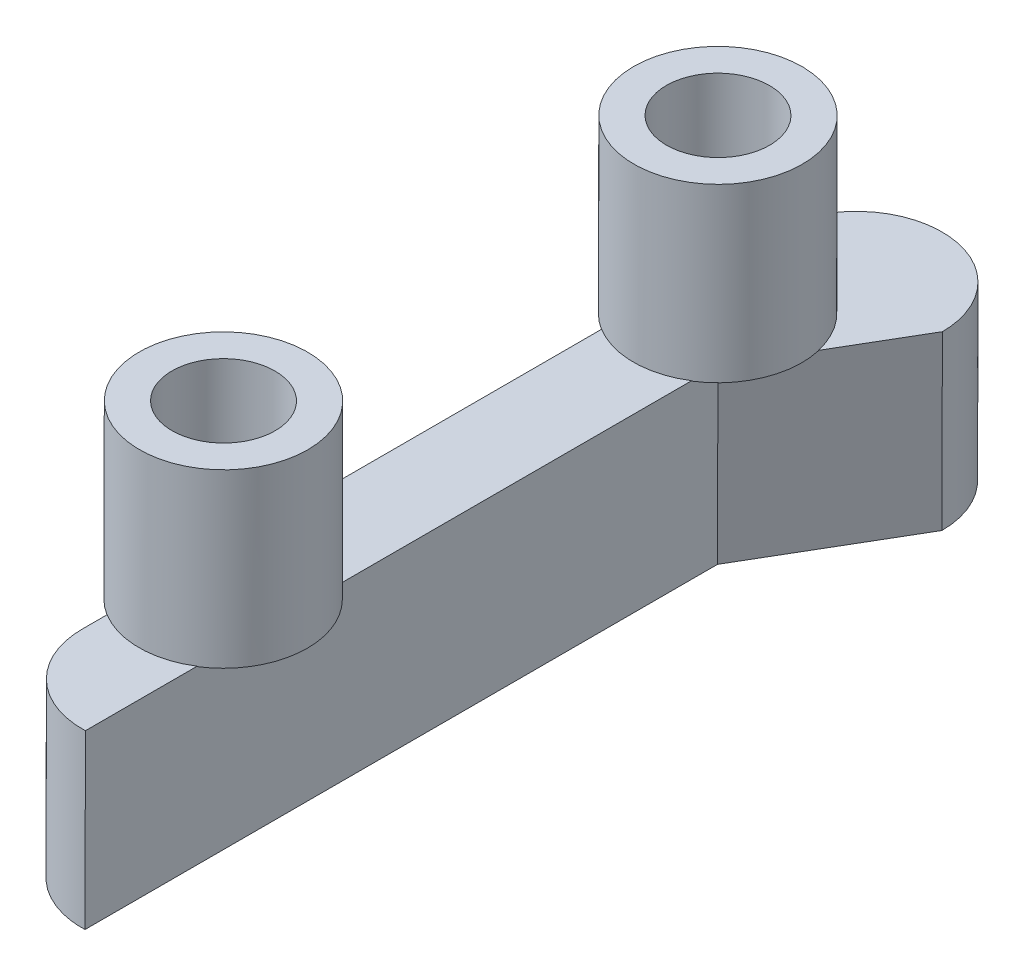
SolidWorks part; units mm, degrees
ref_plane "Front Plane" through (0, 0, 0) normal (0, 0, 1) x (1, 0, 0)
ref_plane "Top Plane" through (0, 0, 0) normal (0, 1, 0) x (1, 0, 0)
ref_plane "Right Plane" through (0, 0, 0) normal (1, 0, 0) x (0, 0, -1)
ref_plane "Plane1" through (0.2124, 88.2612, 0) normal (0.0024, 1, 0) x (1, -0.0024, 0)
sketch "Sketch1" plane through (0.2124, 88.2612, 0) normal (0.0024, 1, 0) x (1, -0.0024, 0)
  line L0 (57.0987, -271.5533) -> (57.0987, -288.7007) construction
  line L1 (57.0987, -271.5533) -> (57.0987, -288.7007)
  line L6 (62.0987, -271.5533) -> (62.0987, -291.5533)
  line L7 (59.6958, -275.6724) -> (62.0987, -271.5533)
  line L8 (59.6958, -295.6724) -> (59.6958, -275.6724)
  line L9 (62.0987, -291.5533) -> (59.6958, -295.6724)
  line L10 (62.0987, -271.5533) -> (62.0987, -291.5533)
  line L11 (59.6958, -275.6724) -> (62.0987, -271.5533)
  line L12 (59.6958, -295.6724) -> (59.6958, -275.6724)
  line L13 (62.0987, -291.5533) -> (59.6958, -295.6724)
  spline S0 degree 3 poles (74.2714, -14284.9704) (55.1287, -54.2949) (54.712, -260.9818) (54.7603, -296.7656) (54.7607, -297.0249) (54.7619, -297.7783) (54.7628, -298.2482) (54.7649, -299.1211) (54.7661, -299.5125) (54.7679, -300.0307) (54.7685, -300.1921) (54.7698, -300.4919) (54.7705, -300.631) (54.7725, -301.0078) (54.7739, -301.2046) (54.776, -301.4206) (54.7767, -301.4792) (54.7782, -301.5694) (54.779, -301.6009) (54.7812, -301.6521) (54.7826, -301.6303) (54.7848, -301.515) (54.7855, -301.4627) (54.787, -301.3296) (54.7877, -301.249) (54.7898, -300.9694) (54.7912, -300.7318) (54.7938, -300.1538) (54.795, -299.8105) (54.7973, -299.0466) (54.7984, -298.6237) (54.7998, -297.9268) (54.8003, -297.6828) (54.8011, -297.1826) (54.8015, -296.9258) (54.8026, -296.1356) (54.8033, -295.5826) (54.804, -294.7126) (54.8042, -294.4169) (54.8046, -293.8239) (54.8047, -293.5252) (54.8051, -292.6227) (54.8052, -292.0106) (54.8051, -290.7765) (54.805, -290.1699) (54.8045, -289.2751) (54.8043, -288.9793) (54.8039, -288.3931) (54.8036, -288.1014) (54.8028, -287.2475) (54.8021, -286.7011) (54.8005, -285.6678) (54.7995, -285.1892) (54.798, -284.5267) (54.7975, -284.3152) (54.7964, -283.911) (54.7958, -283.7178) (54.794, -283.1779) (54.7927, -282.8674) (54.7908, -282.4745) (54.7901, -282.3557) (54.7887, -282.1432) (54.788, -282.0502) (54.7858, -281.8142) (54.7844, -281.7118) (54.7815, -281.6165) (54.78, -281.625) (54.777, -281.753) (54.7756, -281.8714) (54.7735, -282.1316) (54.7728, -282.2328) (54.7714, -282.4597) (54.7707, -282.5855) (54.7688, -282.9991) (54.7675, -283.3228) (54.7657, -283.8827) (54.7652, -284.0814) (54.7641, -284.4956) (54.7636, -284.7121) (54.7621, -285.389) (54.7612, -285.8775) (54.7596, -286.9286) (54.759, -287.4759) (54.7582, -288.3282) (54.758, -288.6176) (54.7576, -289.2072) (54.7574, -289.5089) (54.576, -692.9549) (115.528, -2312.4107) (-708.9989, 13685.6876) knots -2.058294 -2.058294 -2.058294 -2.058294 0.015625 0.015625 0.03125 0.03125 0.0625 0.0625 0.09375 0.09375 0.109375 0.109375 0.125 0.125 0.15625 0.15625 0.171875 0.171875 0.1875 0.1875 0.21875 0.21875 0.234375 0.234375 0.25 0.25 0.28125 0.28125 0.3125 0.3125 0.34375 0.34375 0.359375 0.359375 0.375 0.375 0.40625 0.40625 0.421875 0.421875 0.4375 0.4375 0.46875 0.46875 0.5 0.5 0.515625 0.515625 0.53125 0.53125 0.5625 0.5625 0.59375 0.59375 0.609375 0.609375 0.625 0.625 0.65625 0.65625 0.671875 0.671875 0.6875 0.6875 0.71875 0.71875 0.75 0.75 0.78125 0.78125 0.796875 0.796875 0.8125 0.8125 0.84375 0.84375 0.859375 0.859375 0.875 0.875 0.90625 0.90625 0.9375 0.9375 0.953125 0.953125 0.96875 0.96875 21.802605 21.802605 21.802605 21.802605 only from (57.0987, -291.5533) to (57.0987, -288.7007) construction
  spline S1 degree 3 poles (-1910.3781, 36.9604) (-247.8118, -203.0495) (66.5392, -269.2251) (62.0205, -292.1946) (61.9736, -292.3503) (61.7926, -292.7938) (61.6134, -293.0678) (61.166, -293.5272) (60.8911, -293.7187) (60.4356, -293.9148) (60.2729, -293.9666) (59.9413, -294.0355) (59.7733, -294.053) (59.4329, -294.0536) (59.2605, -294.0361) (58.9299, -293.9681) (58.7677, -293.9171) (58.4602, -293.7853) (58.3161, -293.7055) (58.0458, -293.5194) (57.9204, -293.4132) (57.5835, -293.0674) (57.4046, -292.7935) (57.2236, -292.3498) (57.1767, -292.1937) (52.4327, -268.0389) (401.1252, -199.0816) (2032.0992, 21.2723) knots -8.918573 -8.918573 -8.918573 -8.918573 0.0625 0.0625 0.125 0.125 0.25 0.25 0.375 0.375 0.4375 0.4375 0.5 0.5 0.5625 0.5625 0.625 0.625 0.6875 0.6875 0.75 0.75 0.875 0.875 0.9375 0.9375 10.39234 10.39234 10.39234 10.39234 only from (62.0987, -291.5533) to (57.0987, -291.5533) construction
  spline S2 degree 3 poles (2060.5072, -278.104) (-714.938, -386.1273) (69.1289, -306.7061) (62.0187, -270.9049) (61.9708, -270.7472) (61.8462, -270.4464) (61.7686, -270.3008) (61.5861, -270.0278) (61.4828, -269.9021) (61.2526, -269.6715) (61.1242, -269.5659) (60.8529, -269.3845) (60.7095, -269.3076) (60.4069, -269.1819) (60.2482, -269.1336) (59.9286, -269.0698) (59.766, -269.0534) (59.4354, -269.0532) (59.2729, -269.0693) (58.9531, -269.1326) (58.7941, -269.1807) (58.4914, -269.3059) (58.3478, -269.3826) (58.076, -269.5638) (57.9474, -269.6692) (57.6017, -270.0144) (57.4153, -270.2929) (51.9934, -283.3333) (151.5758, -346.1818) (979.9657, 1500.3149) knots -13.735207 -13.735207 -13.735207 -13.735207 0.0625 0.0625 0.125 0.125 0.1875 0.1875 0.25 0.25 0.3125 0.3125 0.375 0.375 0.4375 0.4375 0.5 0.5 0.5625 0.5625 0.625 0.625 0.6875 0.6875 0.75 0.75 0.875 0.875 6.172444 6.172444 6.172444 6.172444 only from (62.0987, -271.5533) to (57.0987, -271.5533) construction
  spline S3 degree 3 poles (57.0987, -291.5533) (57.0987, -291.5) (57.0987, -291.4467) (57.0989, -290.776) (57.099, -290.169) (57.0989, -289.2792) (57.0988, -288.9887) (57.0987, -288.7007) knots 0.46605 0.46605 0.46605 0.46605 0.46875 0.46875 0.5 0.5 0.515337 0.515337 0.515337 0.515337
  spline S4 degree 3 poles (62.0987, -291.5533) (62.0987, -291.7163) (62.0829, -291.8771) (62.0205, -292.1946) (61.9736, -292.3503) (61.7926, -292.7938) (61.6134, -293.0678) (61.166, -293.5272) (60.8911, -293.7187) (60.4356, -293.9148) (60.2729, -293.9666) (59.9413, -294.0355) (59.7733, -294.053) (59.4329, -294.0536) (59.2605, -294.0361) (58.9299, -293.9681) (58.7677, -293.9171) (58.4602, -293.7853) (58.3161, -293.7055) (58.0458, -293.5194) (57.9204, -293.4132) (57.5835, -293.0674) (57.4046, -292.7935) (57.2236, -292.3498) (57.1767, -292.1937) (57.1144, -291.8765) (57.0987, -291.7159) (57.0987, -291.5533) knots 0 0 0 0 0.0625 0.0625 0.125 0.125 0.25 0.25 0.375 0.375 0.4375 0.4375 0.5 0.5 0.5625 0.5625 0.625 0.625 0.6875 0.6875 0.75 0.75 0.875 0.875 0.9375 0.9375 1 1 1 1
  spline S5 degree 3 poles (62.0987, -271.5533) (62.0987, -271.3901) (62.0829, -271.2277) (62.0187, -270.9049) (61.9708, -270.7472) (61.8462, -270.4464) (61.7686, -270.3008) (61.5861, -270.0278) (61.4828, -269.9021) (61.2526, -269.6715) (61.1242, -269.5659) (60.8529, -269.3845) (60.7095, -269.3076) (60.4069, -269.1819) (60.2482, -269.1336) (59.9286, -269.0698) (59.766, -269.0534) (59.4354, -269.0532) (59.2729, -269.0693) (58.9531, -269.1326) (58.7941, -269.1807) (58.4914, -269.3059) (58.3478, -269.3826) (58.076, -269.5638) (57.9474, -269.6692) (57.6017, -270.0144) (57.4153, -270.2929) (57.1653, -270.8941) (57.0987, -271.2226) (57.0987, -271.5533) knots 0 0 0 0 0.0625 0.0625 0.125 0.125 0.1875 0.1875 0.25 0.25 0.3125 0.3125 0.375 0.375 0.4375 0.4375 0.5 0.5 0.5625 0.5625 0.625 0.625 0.6875 0.6875 0.75 0.75 0.875 0.875 1 1 1 1
  dimension "D1" = 0
extrude "Boss-Extrude1" add sketch "Sketch1" against normal blind 5 and the other way blind 0.01 contours S5 L1 S3 S4 region at (58.932, 88.1199, 280.2414)
sketch "Sketch5" plane through (0.2124, 88.2612, 0) normal (0.0024, 1, 0) x (1, -0.0024, 0)
  line L0 (58.3824, -274.3691) -> (58.3824, -288.7375) construction
  line L1 (58.3824, -293.7375) -> (58.3824, -269.3691) construction
  line L9 (59.6662, -281.5533) -> (57.0987, -281.5533) construction
  line L10 (59.6662, -275.6724) -> (59.6662, -291.6335) construction
  line L11 (57.0987, -271.5533) -> (57.0987, -288.7007) construction
  circle A6 centre (58.3824, -274.3691) radius 2.45
  circle A7 centre (58.3824, -274.3691) radius 1.5
  circle A8 centre (58.3824, -288.7375) radius 2.45
  circle A9 centre (58.3824, -288.7375) radius 1.5
  spline S2 degree 3 poles (59.6958, -294.0514) (59.665, -294.0526) (59.6341, -294.0532) (59.4329, -294.0536) (59.2605, -294.0361) (58.9299, -293.9681) (58.7677, -293.9171) (58.4602, -293.7853) (58.3161, -293.7055) (58.0458, -293.5194) (57.9204, -293.4132) (57.5835, -293.0674) (57.4046, -292.7935) (57.2236, -292.3498) (57.1767, -292.1937) (57.1144, -291.8765) (57.0987, -291.7159) (57.0987, -291.5533) knots 0.488632 0.488632 0.488632 0.488632 0.5 0.5 0.5625 0.5625 0.625 0.625 0.6875 0.6875 0.75 0.75 0.875 0.875 0.9375 0.9375 1 1 1 1 construction
  spline S3 degree 3 poles (62.0987, -271.5533) (62.0987, -271.3901) (62.0829, -271.2277) (62.0187, -270.9049) (61.9708, -270.7472) (61.8462, -270.4464) (61.7686, -270.3008) (61.5861, -270.0278) (61.4828, -269.9021) (61.2526, -269.6715) (61.1242, -269.5659) (60.8529, -269.3845) (60.7095, -269.3076) (60.4069, -269.1819) (60.2482, -269.1336) (59.9286, -269.0698) (59.766, -269.0534) (59.4354, -269.0532) (59.2729, -269.0693) (58.9531, -269.1326) (58.7941, -269.1807) (58.4914, -269.3059) (58.3478, -269.3826) (58.076, -269.5638) (57.9474, -269.6692) (57.6017, -270.0144) (57.4153, -270.2929) (57.1653, -270.8941) (57.0987, -271.2226) (57.0987, -271.5533) knots 0 0 0 0 0.0625 0.0625 0.125 0.125 0.1875 0.1875 0.25 0.25 0.3125 0.3125 0.375 0.375 0.4375 0.4375 0.5 0.5 0.5625 0.5625 0.625 0.625 0.6875 0.6875 0.75 0.75 0.875 0.875 1 1 1 1 construction
  point P20 (58.3824, -281.5533)
  point P21 (58.3824, -281.5533)
  dimension "D1" = 4.9
  dimension "D2" = 3
  dimension "D3" = 5
extrude "Boss-Extrude2" add sketch "Sketch5" along normal blind 5
